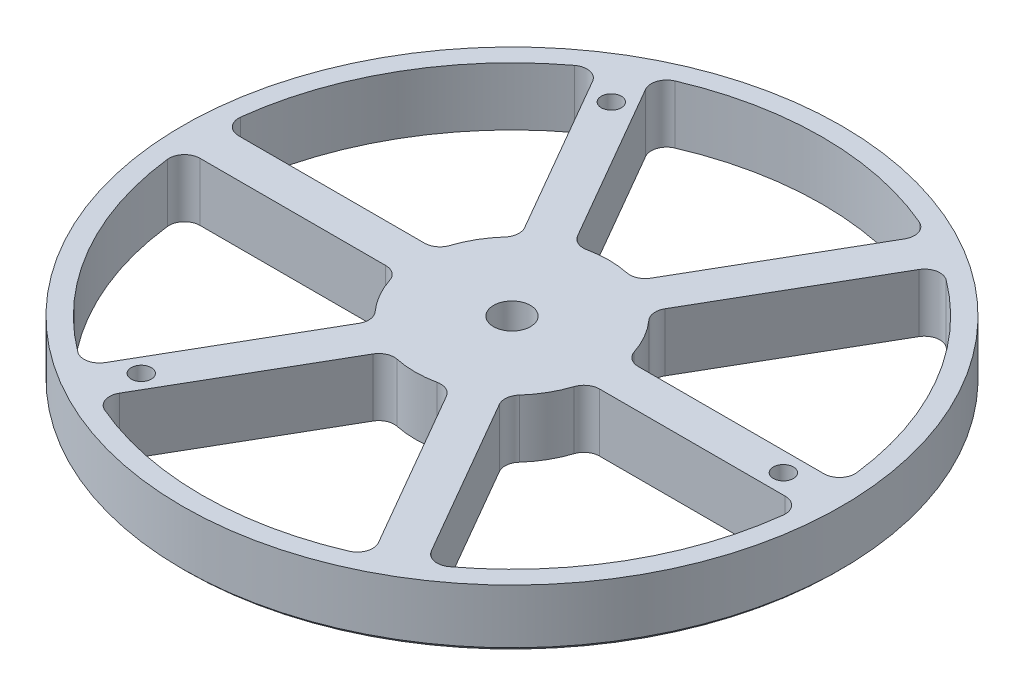
SolidWorks part; units mm, degrees
ref_plane "Front Plane" through (0, 0, 0) normal (0, 0, 1) x (1, 0, 0)
ref_plane "Top Plane" through (0, 0, 0) normal (0, 1, 0) x (1, 0, 0)
ref_plane "Right Plane" through (0, 0, 0) normal (1, 0, 0) x (0, 0, -1)
sketch "Sketch2" plane through (0, 0, 0) normal (1, 0, 0) x (0, 0, -1)
  line L0 (0, 0) -> (-84.9998, 0)
  line L1 (-84.9998, 0) -> (-84.9998, 15)
  line L2 (-84.9998, 15) -> (0, 15)
  line L5 (0, 15) -> (0, 0)
  dimension "D1" = 84.9998
  dimension "D2" = 15
ref_axis "Axis1" through (0, -0.75, 0) along (0, 1, 0)
revolve "Revolve1" add sketch "Sketch2" angle 360 about axis through (0, -0.75, 0) along (0, 1, 0)
hole_wizard "#6 (0.204) Diameter Hole1" positions "Sketch6" profile "Sketch7" hole size "#6" standard "ANSI Inch" end condition through all
sketch "Sketch6" plane through (0, 15, 0) normal (0, 1, 0) x (1, 0, 0)
  line L0 (0, 0) -> (-69.8201, 120.932) construction
  line L2 (0, 0) -> (0, 109.0908) construction
  point P0 (-35, 60.6218)
  dimension "D1" = 30
  dimension "D2" = 70
sketch "Sketch7" plane through (-35, 15, -60.6218) normal (1, 0, 0) x (0, 0, 1)
  line L0 (0, 0) -> (0, 15)
  line L1 (0, 15) -> (2.5908, 15)
  line L2 (2.5908, 15) -> (2.5908, 0)
  line L5 (2.5908, 0) -> (0, 0)
  line L11 (0, -6.35) -> (0, 107.95) construction
  dimension "Thru Hole Dia." = 5.1816
  dimension "Thru Hole Depth" = 15
pattern_circular "CirPattern3" count 3 over 360 about axis through (0, -0.75, 0) along (0, 1, 0) of "#6 (0.204) Diameter Hole1"
sketch "Sketch8" plane through (0, 15, 0) normal (0, 1, 0) x (1, 0, 0)
  line L4 (0, 0) -> (0, 93.9995) construction
  line L5 (0, 0) -> (113.8372, 0) construction
  line L6 (-7.9173, 23.7132) -> (-35.5916, 71.6464)
  line L7 (7.9173, 23.7132) -> (35.5916, 71.6464)
  line L8 (0, 0) -> (-35, 60.6218) construction
  arc A0 (-7.9173, 23.7132) -> (7.9173, 23.7132) centre (0, 0) cw
  arc A1 (-35.5916, 71.6464) -> (35.5916, 71.6464) centre (0, 0) cw
  circle A2 centre (0, 0) radius 84.9998 construction
  dimension "D1" = 25
  dimension "D2" = 5
  dimension "D3" = 5
extrude "Cut-Extrude1" cut sketch "Sketch8" against normal through all
fillet "Fillet1" radius 4 4 edges at (7.9173, 7.5, -23.7132) (35.5916, 7.5, -71.6464) (-7.9173, 7.5, -23.7132) (-35.5916, 7.5, -71.6464)
pattern_circular "CirPattern4" count 6 over 360 about axis through (0, -0.75, 0) along (0, 1, 0) of "Cut-Extrude1", "Fillet1"
chamfer "Chamfer2" distance 1 angle 45 1 edges at (0, 0, -84.9998)
hole_wizard "3/8 (0.375) Diameter Hole1" positions "Sketch9" profile "Sketch11" hole size "3/8" standard "ANSI Inch" end condition through all
sketch "Sketch9" plane through (0, 0, 0) normal (0, -1, 0) x (-1, 0, 0)
  point P0 (0, 0)
sketch "Sketch11" plane through (0, 0, 0) normal (1, 0, 0) x (0, 0, -1)
  line L0 (0, 0) -> (0, 15)
  line L1 (0, 15) -> (4.7625, 15)
  line L2 (4.7625, 15) -> (4.7625, 0)
  line L5 (4.7625, 0) -> (0, 0)
  line L11 (0, -6.35) -> (0, 107.95) construction
  dimension "Thru Hole Dia." = 9.525
  dimension "Thru Hole Depth" = 15
equation "\"TubeDiameter\" = 6.6929in"
equation "\"D1@Sketch2\"=\"TubeDiameter\"/2"
